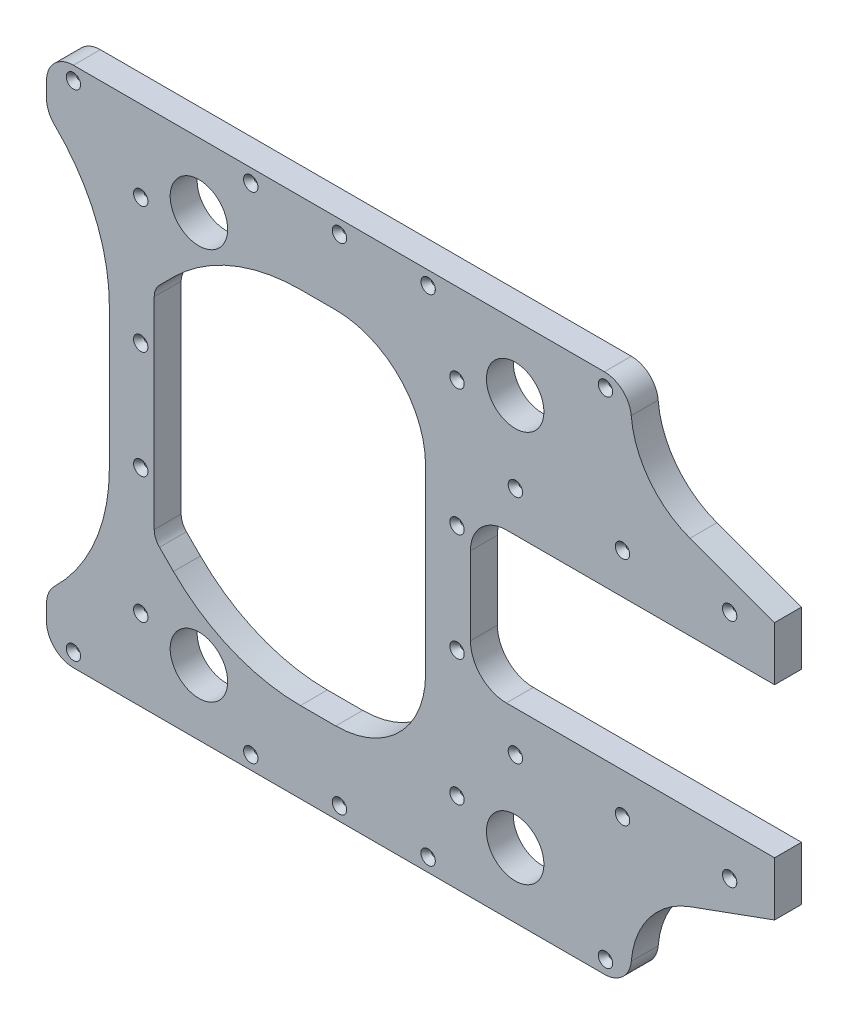
SolidWorks part; units mm, degrees
material "Beech"
ref_plane "Front Plane" through (0, 0, 0) normal (0, 0, 1) x (1, 0, 0)
ref_plane "Top Plane" through (0, 0, 0) normal (0, 1, 0) x (1, 0, 0)
ref_plane "Right Plane" through (0, 0, 0) normal (1, 0, 0) x (0, 0, -1)
sketch "Sketch1" plane through (0, 0, 0) normal (0, 0, 1) x (1, 0, 0)
  line L0 (571.7191, -350) -> (38.3191, -350) construction
  line L1 (571.7191, 19.05) -> (158.4144, 19.05)
  line L2 (571.7191, 19.05) -> (571.7191, -350)
  line L3 (571.7191, -350) -> (158.4144, -350)
  line L4 (158.4144, 19.05) -> (158.4144, -350)
  line L7 (234.6144, -330.95) -> (234.6144, 0) construction
  dimension "D1" = 76.2
extrude "Boss-Extrude1" add sketch "Sketch1" along normal blind 19.05
hole_wizard "1 (1.6) Diameter Hole1" positions "Sketch5" profile "Sketch6" hole size "1" standard "ANSI Inch" end condition up to next
sketch "Sketch5" plane through (0, 0, 19.05) normal (0, 0, 1) x (1, 0, 0)
  point P0 (489.8579, -26.924)
  point P2 (489.8579, -304.026)
  point P4 (266.2109, -26.924)
  point P6 (266.2109, -304.026)
sketch "Sketch6" plane through (489.8579, -26.924, 19.05) normal (1, 0, 0) x (0, -1, 0)
  line L0 (0, 0) -> (0, 19.05)
  line L1 (0, 19.05) -> (20.32, 19.05)
  line L2 (20.32, 19.05) -> (20.32, 0)
  line L5 (20.32, 0) -> (0, 0)
  line L11 (0, -6.35) -> (0, 107.95) construction
  dimension "Thru Hole Dia." = 40.64
  dimension "Thru Hole Depth" = 19.05
sketch "Sketch2" plane through (0, 0, 19.05) normal (0, 0, 1) x (1, 0, 0)
  line L0 (439.2114, -165.475) -> (234.6144, -165.475) construction
  line L1 (439.2114, -330.95) -> (439.2114, 0) construction
  line L2 (234.6144, -330.95) -> (234.6144, 0) construction
  line L3 (571.7191, 0) -> (38.3191, 0) construction
  line L4 (285.4144, -292.85) -> (426.5114, -292.85)
  line L5 (234.6144, -242.05) -> (234.6144, -88.9)
  line L6 (285.4144, -38.1) -> (426.5114, -38.1)
  line L7 (426.5114, -292.85) -> (426.5114, -38.1)
  line L8 (234.6144, -292.85) -> (426.5114, -38.1) construction
  line L9 (234.6144, -38.1) -> (426.5114, -292.85) construction
  line L10 (634.3769, -165.475) -> (509.0614, -165.475) construction
  line L11 (202.8644, -165.475) -> (158.4144, -165.475) construction
  line L12 (634.3769, -203.575) -> (509.0614, -203.575) construction
  line L13 (634.3769, -127.375) -> (509.0614, -127.375) construction
  line L14 (571.7191, -350) -> (571.7191, 19.05) construction
  line L15 (458.2614, -330.95) -> (458.2614, 0) construction
  line L16 (158.4144, 19.05) -> (158.4144, -350) construction
  line L17 (202.8644, -19.05) -> (158.4144, -19.05)
  line L18 (202.8644, -19.05) -> (202.8644, -311.9)
  line L19 (202.8644, -311.9) -> (158.4144, -311.9)
  line L20 (158.4144, -19.05) -> (158.4144, -311.9)
  line L21 (215.5644, -311.9) -> (38.3191, -311.9) construction
  line L22 (234.6144, -88.9) -> (285.4144, -38.1)
  line L23 (234.6144, -242.05) -> (285.4144, -292.85)
  arc A0 (634.3769, -203.575) -> (634.3769, -127.375) centre (634.3769, -165.475) ccw construction
  arc A1 (509.0614, -127.375) -> (509.0614, -203.575) centre (509.0614, -165.475) ccw construction
  point P6 (330.5629, -165.475)
  point P17 (571.7191, -165.475)
  point P25 (470.9614, -165.475)
  dimension "D3" = 38.1
  dimension "D1" = 38.1
  dimension "D2" = 12.7
  dimension "D4" = 12.7
  dimension "D5" = 76.2
  dimension "D6" = 44.45
  dimension "D7" = 146.425
extrude "Cut-Extrude1" cut sketch "Sketch2" against normal through all
sketch "Sketch3" plane through (0, 0, 19.05) normal (0, 0, 1) x (1, 0, 0)
  line L0 (571.7191, -165.475) -> (202.8644, -165.475) construction
  line L1 (571.7191, -350) -> (571.7191, 19.05) construction
  line L2 (202.8644, -311.9) -> (202.8644, -19.05) construction
  line L3 (571.7191, -165.475) -> (673.3191, -165.475) construction
  line L4 (673.3191, -256.55) -> (673.3191, -74.4)
  line L5 (673.3191, -74.4) -> (571.7191, -37.4206)
  line L6 (571.7191, -37.4206) -> (571.7191, -293.5294)
  line L7 (1188.5114, -74.4) -> (673.3191, -74.4) construction
  line L8 (673.3191, -256.55) -> (571.7191, -293.5294)
  dimension "D1" = 101.6
  dimension "D2" = 20
extrude "Boss-Extrude2" add sketch "Sketch3" against normal through all
sketch "Sketch4" plane through (0, 0, 19.05) normal (0, 0, 1) x (1, 0, 0)
  line L0 (673.3191, -165.475) -> (458.2614, -165.475) construction
  line L1 (673.3191, -256.55) -> (673.3191, -74.4) construction
  line L2 (458.2614, -330.95) -> (458.2614, 0) construction
  line L3 (515.4114, -165.475) -> (616.1691, -165.475) construction
  line L4 (515.4114, -133.725) -> (616.1691, -133.725)
  line L5 (515.4114, -197.225) -> (616.1691, -197.225)
  arc A0 (515.4114, -133.725) -> (515.4114, -197.225) centre (515.4114, -165.475) ccw
  arc A1 (616.1691, -197.225) -> (616.1691, -133.725) centre (616.1691, -165.475) ccw
  point P8 (565.7903, -165.475)
  dimension "D2" = 25.4
  dimension "D1" = 63.5
extrude "Cut-Extrude2" cut sketch "Sketch4" against normal through all
fillet "Fillet1" radius 127 2 edges at (202.8644, -311.9, 9.525) (202.8644, -19.05, 9.525)
fillet "Fillet2" radius 63.5 4 edges at (426.5114, -292.85, 9.525) (426.5114, -38.1, 9.525) (571.7191, -293.5294, 9.525) (571.7191, -37.4206, 9.525)
fillet "Fillet3" radius 19.05 6 edges at (158.4144, -19.05, 9.525) (158.4144, 19.05, 9.525) (158.4144, -311.9, 9.525) (158.4144, -350, 9.525) (571.7191, -350, 9.525) (571.7191, 19.05, 9.525)
sketch "Sketch7" plane through (0, 0, 19.05) normal (0, 0, 1) x (1, 0, 0)
  line L0 (673.3191, -256.55) -> (673.3191, -74.4) construction
  line L1 (673.3191, -112.5) -> (458.2614, -112.5)
  line L2 (673.3191, -112.5) -> (673.3191, -218.45)
  line L3 (673.3191, -218.45) -> (458.2614, -218.45)
  line L4 (458.2614, -112.5) -> (458.2614, -218.45)
extrude "Cut-Extrude3" cut sketch "Sketch7" against normal through all
fillet "Fillet4" radius 25.4 2 edges at (458.2614, -218.45, 9.525) (458.2614, -112.5, 9.525)
hole_wizard "Hole1" positions "Sketch8" profile "Sketch9" legacy
sketch "Sketch8" plane through (-151.6484, -165.475, 19.05) normal (0, 0, 1) x (0, -1, 0)
  line L0 (-175, 310.0628) -> (-175, 724.4414) construction
  line L3 (-81.55, 824.9675) -> (-81.55, 609.9098) construction
  line L7 (-165.475, 600.3848) -> (0, 600.3848) construction
  line L9 (-175, 376.7378) -> (0, 376.7378) construction
  line L12 (0, 3.9184) -> (0, 227.5654) construction
  point P20 (-81.55, 717.4386)
  point P22 (-81.55, 641.6598)
  point P24 (-81.55, 793.2175)
  point P27 (-175, 705.3914)
  point P29 (-175, 329.1128)
  point P32 (-175, 579.9652)
  point P34 (-175, 454.539)
  point P35 (-175, 517.2521)
  point P50 (-127.375, 600.3848)
  point P52 (-38.1, 600.3848)
  point P61 (-127.375, 376.7378)
  point P63 (-38.1, 376.7378)
  point P74 (38.1, 376.7378)
  point P75 (127.375, 376.7378)
  point P76 (38.1, 600.3848)
  point P77 (127.375, 600.3848)
  point P78 (175, 517.2521)
  point P79 (175, 454.539)
  point P80 (175, 579.9652)
  point P81 (175, 329.1128)
  point P82 (175, 705.3914)
  point P83 (81.55, 793.2175)
  point P84 (81.55, 641.6598)
  point P85 (81.55, 717.4386)
sketch "Sketch9" plane through (565.7903, -247.025, 19.05) normal (1, 0, 0) x (0, -1, 0)
  line L0 (0, 0) -> (0, 39.0539)
  line L1 (0, 39.0539) -> (1.5875, 38.1)
  line L2 (1.5875, 38.1) -> (1.5875, 4.0177)
  line L3 (1.5875, 4.0177) -> (5.08, 0)
  line L4 (5.08, 0) -> (0, 0)
  line L5 (0, -14.3089) -> (0, 102.4216) construction
  line L6 (0, 39.0539) -> (-1.5875, 38.1) construction
  line L7 (-1.5875, 4.0177) -> (-5.08, 0) construction
  dimension "Diameter" = 3.175
  dimension "Depth" = 38.1
  dimension "C-Sink Diameter" = 10.16
  dimension "C-Sink Angle" = 82
  dimension "Drill Angle" = 118
hole_wizard "Hole2" [suppressed] positions "Sketch10" profile "Sketch11"
sketch "Sketch10" plane through (-151.6484, -256.55, -470.1861) normal (0, -1, 0) x (-0.3746, 0, -0.9272)
  point P1 (-659.7862, 411.7841)
  point P3 (-615.2409, 429.7815)
  point P5 (-711.4987, 766.922)
  point P7 (-796.2804, 732.668)
  point P9 (-889.1694, 1044.5267)
  point P11 (-923.7091, 1031.114)
sketch "Sketch11" plane through (477.3114, -256.55, -12.7) normal (1, 0, 0) x (0, 0, -1)
  line L0 (0, 0) -> (0, 39.0539)
  line L1 (0, 39.0539) -> (1.5875, 38.1)
  line L2 (1.5875, 38.1) -> (1.5875, 4.0177)
  line L3 (1.5875, 4.0177) -> (5.08, 0)
  line L4 (5.08, 0) -> (0, 0)
  line L5 (0, -14.3089) -> (0, 102.4216) construction
  line L6 (0, 39.0539) -> (-1.5875, 38.1) construction
  line L7 (-1.5875, 4.0177) -> (-5.08, 0) construction
  dimension "Diameter" = 3.175
  dimension "Depth" = 38.1
  dimension "C-Sink Diameter" = 10.16
  dimension "C-Sink Angle" = 82
  dimension "Drill Angle" = 118
fillet "Fillet5" radius 12.7 2 edges at (234.6144, -242.05, 9.525) (234.6144, -88.9, 9.525)
fillet "Fillet6" radius 127 2 edges at (285.4144, -292.85, 9.525) (285.4144, -38.1, 9.525)
